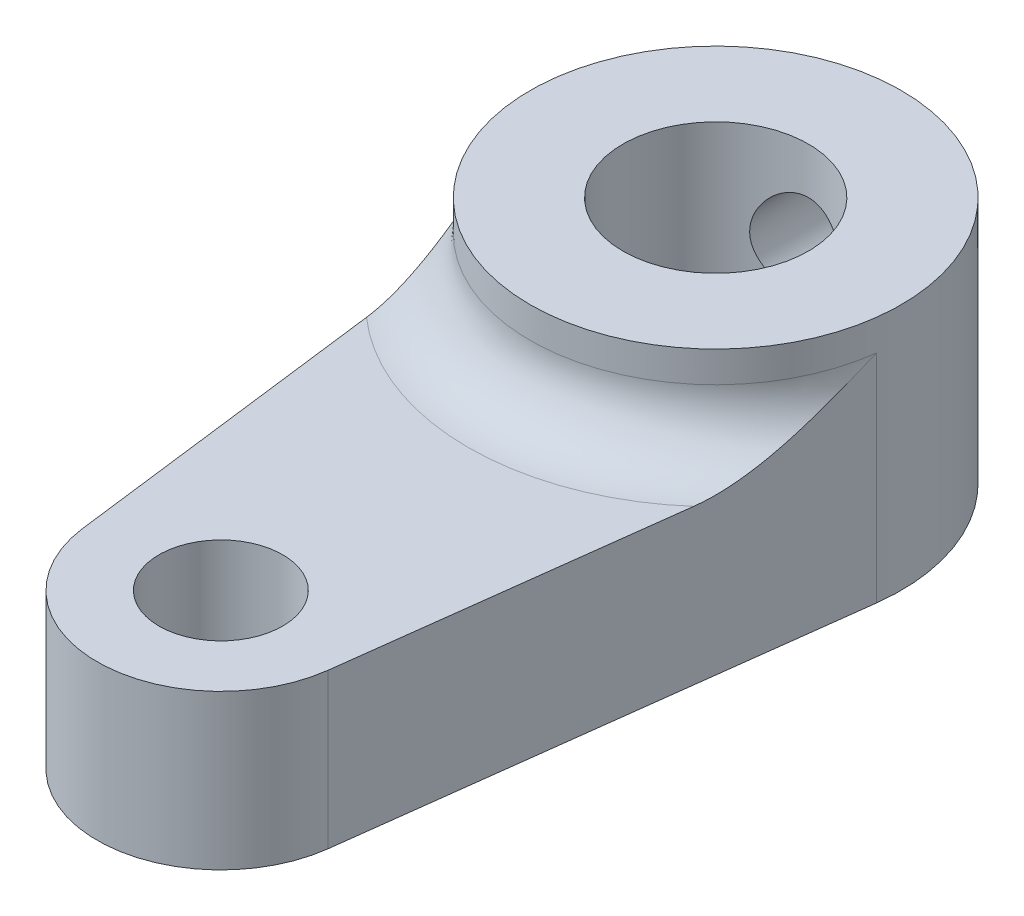
SolidWorks part; units mm, degrees
note: The reader was unsure of these and kept them because the rebuilt part matched: shared geometry of "Sketch1<3>".
ref_plane "Front Plane" through (0, 0, 0) normal (0, 0, 1) x (1, 0, 0)
ref_plane "Top Plane" through (0, 0, 0) normal (0, 1, 0) x (1, 0, 0)
ref_plane "Right Plane" through (0, 0, 0) normal (1, 0, 0) x (0, 0, -1)
sketch "Sketch1" plane through (0, 0, 0) normal (0, 1, 0) x (1, 0, 0)
  line L0 (0, 0) -> (0, -16) construction
  line L1 (-5.9529, -0.75) -> (-3.9686, -16.5)
  line L2 (5.9529, -0.75) -> (3.9686, -16.5)
  circle A0 centre (0, 0) radius 6
  circle A1 centre (0, -16) radius 4
  circle A2 centre (0, -16) radius 2
  dimension "D1" = 12
  dimension "D2" = 8
  dimension "D3" = 4
  dimension "D4" = 16
extrude "Boss-Extrude1" add sketch "Sketch1" along normal blind 5
extrude "Boss-Extrude2" add sketch "Sketch1<3>" along normal blind 3 from offset 5 contours A0
sketch "Sketch1<3>" plane through (0, 0, 0) normal (0, 1, 0) x (1, 0, 0) same geometry as "Sketch1"
fillet "Fillet1" radius 2 1 edges at (0, 5, 6)
sketch "Sketch2" plane through (0, 8, 0) normal (0, 1, 0) x (1, 0, 0)
  circle A0 centre (0, 0) radius 3
  dimension "D1" = 6
extrude "Cut-Extrude1" cut sketch "Sketch2" against normal through all
sketch "Sketch3" plane through (0, 0, 0) normal (0, -1, 0) x (1, 0, 0)
  line L0 (-6.0655, -8.1903) -> (6.2783, -8.1903)
surface "Surface-Extrude1" sketch "Sketch3" parameters "D1"=8
hole_wizard "M3 Tapped Hole1" positions "Sketch4" profile "Sketch5" tap size "M3" standard "ISO"
sketch "Sketch4" plane through (0, 0, -8.1903) normal (0, 0, 1) x (1, 0, 0)
  point P0 (0, 5)
  dimension "D1" = 5
sketch "Sketch5" plane through (0, 5, -8.1903) normal (1, 0, 0) x (0, 1, 0)
  line L0 (0, 0) -> (0, 9.4013)
  line L1 (0, 9.4013) -> (1.5, 8.5)
  line L2 (1.5, 8.5) -> (1.5, 0.025)
  line L3 (1.5, 0.025) -> (1.525, 0)
  line L5 (1.525, 0) -> (0, 0)
  line L6 (-1.5, 0.025) -> (-1.525, 0) construction
  line L10 (0, 9.4013) -> (-1.5, 8.5) construction
  line L11 (0, -6.35) -> (0, 107.95) construction
  dimension "Tap Drill Dia." = 3
  dimension "Tap Drill Depth" = 8.5
  dimension "Near C'Sink Dia." = 3.05
  dimension "Near C'Sink Angle" = 90
  dimension "Drill Angle" = 118
cosmetic thread "Hole Thread1" parameters "D1"=5.5922, "D2"=3
